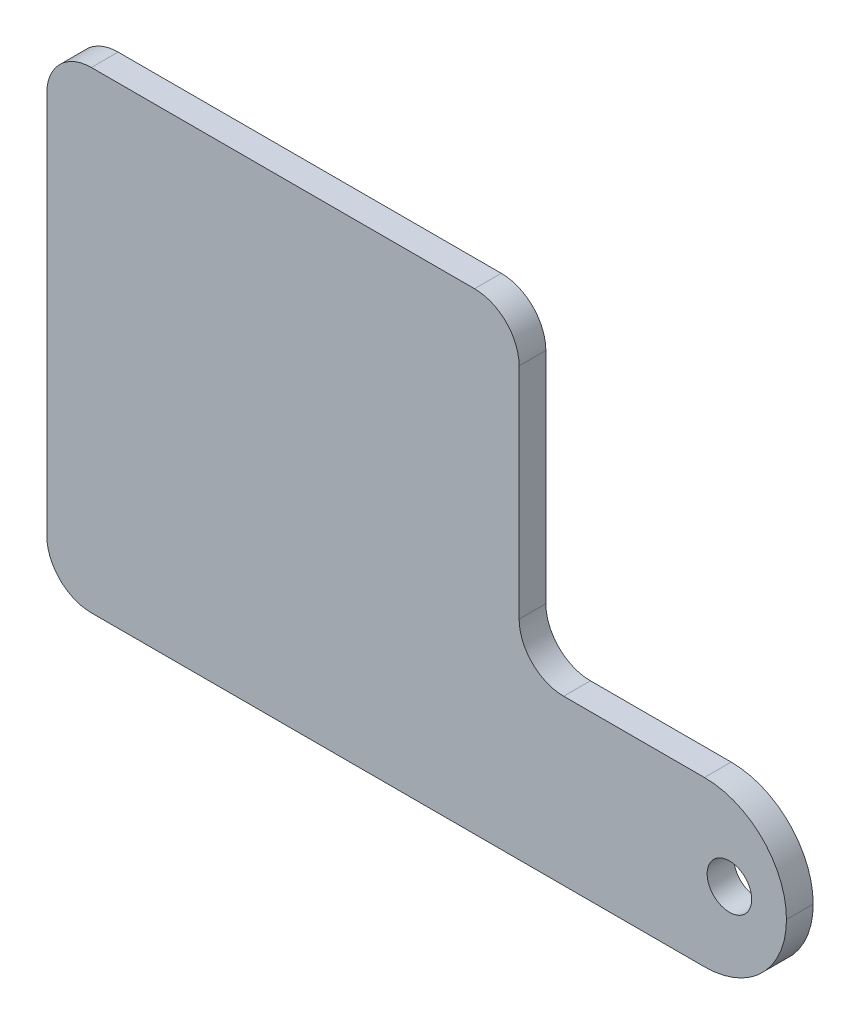
SolidWorks part; units mm, degrees
ref_plane "Front Plane" through (0, 0, 0) normal (0, 0, 1) x (1, 0, 0)
ref_plane "Top Plane" through (0, 0, 0) normal (0, 1, 0) x (1, 0, 0)
ref_plane "Right Plane" through (0, 0, 0) normal (1, 0, 0) x (0, 0, -1)
sketch "Sketch1" plane through (0, 0, 0) normal (0, 0, 1) x (1, 0, 0)
  line L0 (53, 53) -> (53, 18.4)
  line L1 (0, 0) -> (83, 0)
  line L2 (0, 0) -> (0, 53)
  line L3 (0, 53) -> (53, 53)
  line L4 (83, 0) -> (83, 18.4)
  line L5 (53, 18.4) -> (83, 18.4)
  circle A0 centre (76.6, 9.2) radius 2.5
  dimension "D7" = 5
  dimension "D1" = 53
  dimension "D2" = 83
  dimension "D3" = 53
  dimension "D4" = 18.4
  dimension "D5" = 9.2
  dimension "D6" = 6.4
extrude "Boss-Extrude1" add sketch "Sketch1" along normal blind 3
fillet "Fillet1" radius 5 3 edges at (0, 53, 1.5) (0, 0, 1.5) (53, 53, 1.5)
fillet "Fillet2" radius 5 1 edges at (53, 18.4, 1.5)
fillet "Fillet4" radius 9.2 2 edges at (83, 0, 1.5) (83, 18.4, 1.5)
